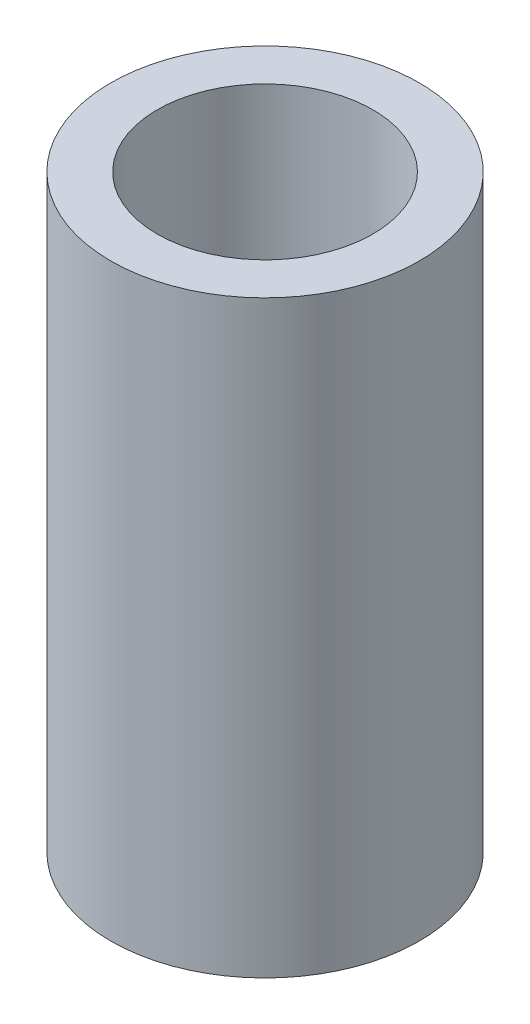
SolidWorks part; units mm, degrees
ref_plane "Front Plane" through (0, 0, 0) normal (0, 0, 1) x (1, 0, 0)
ref_plane "Top Plane" through (0, 0, 0) normal (0, 1, 0) x (1, 0, 0)
ref_plane "Right Plane" through (0, 0, 0) normal (1, 0, 0) x (0, 0, -1)
sketch "Sketch1" plane through (0, 0, 0) normal (0, 1, 0) x (1, 0, 0)
  circle A0 centre (0, 0) radius 22.5
  dimension "SLEEVE_OD" = 45
extrude "Boss-Extrude1" add sketch "Sketch1" along normal blind 85.9013
sketch "Sketch2" plane through (0, 0, 0) normal (0, 1, 0) x (1, 0, 0)
  circle A0 centre (0, 0) radius 15.7173
  dimension "BORE_D" = 31.4345
extrude "Cut-Extrude1" cut sketch "Sketch2" along normal through all
chamfer "Chamfer1" distance 3.087 angle 55.938 rebuild error yes
